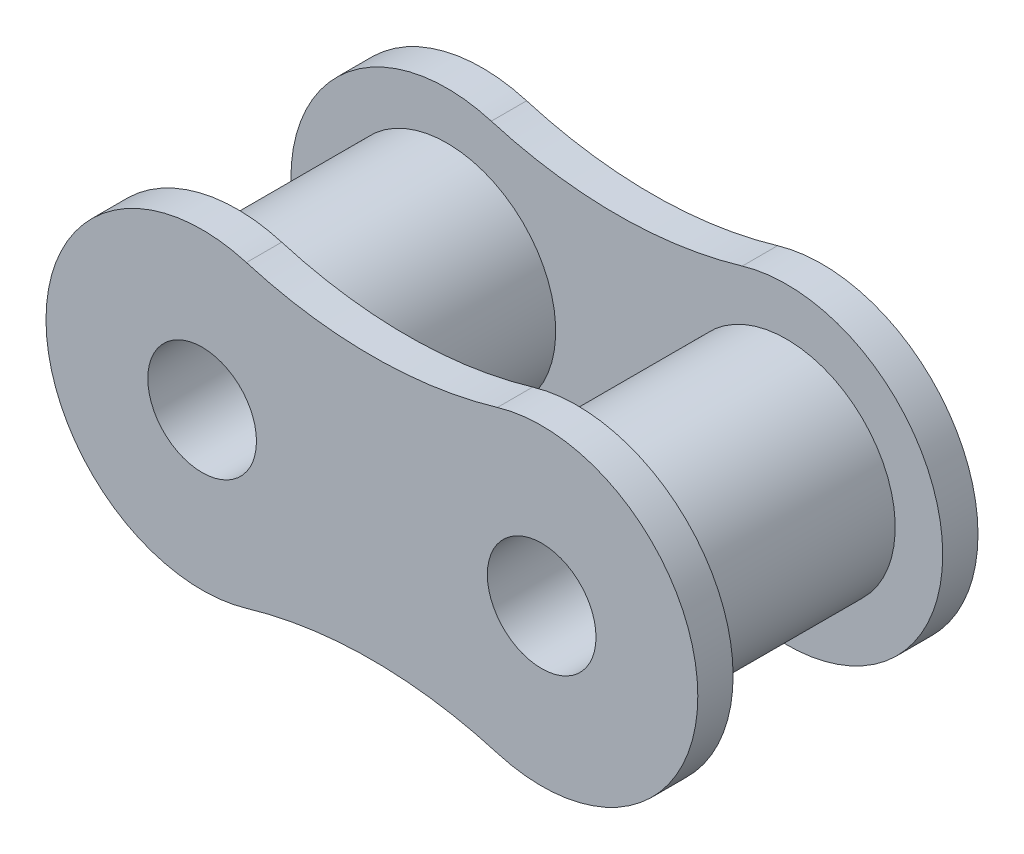
SolidWorks part; units mm, degrees
ref_plane "Front Plane" through (0, 0, 0) normal (0, 0, 1) x (1, 0, 0)
ref_plane "Top Plane" through (0, 0, 0) normal (0, 1, 0) x (1, 0, 0)
ref_plane "Right Plane" through (0, 0, 0) normal (1, 0, 0) x (0, 0, -1)
ref_axis "Axis_X" through (-24.6988, 0, 0) along (1, 0, 0)
ref_axis "Axis_Y" through (0, 8.03, 0) along (0, -1, 0)
ref_axis "Axis_Z" through (0, 0, -7.205) along (0, 0, 1)
sketch "Sketch1" plane through (0, 0, 0) normal (0, 0, 1) x (1, 0, 0)
  line L0 (0, 0) -> (-15.875, 0) construction
  line L1 (0, 5.08) -> (0, -5.08) construction
  circle A0 centre (0, 0) radius 2.54
  circle A1 centre (0, 0) radius 5.08
  circle A2 centre (-15.875, 0) radius 2.54
  circle A3 centre (-15.875, 0) radius 5.08
  dimension "FIX_41" = 5.08
  dimension "FIX_42" = 10.16
  dimension "FIX_43" = 15.875
extrude "Boss-Extrude1" add sketch "Sketch1" along normal mid plane 9.8
sketch "Sketch2" plane through (0, 0, 4.9) normal (0, 0, 1) x (1, 0, 0)
  line L0 (-15.875, 0) -> (0, 0) construction
  circle A0 centre (0, 0) radius 2.54
  circle A1 centre (-15.875, 0) radius 2.54
  arc A2 (-2.0702, -7.0003) -> (-2.0702, 7.0003) centre (0, 0) ccw
  arc A3 (-13.8048, 7.0003) -> (-13.8048, -7.0003) centre (-15.875, 0) ccw
  arc A4 (-13.8048, 7.0003) -> (-2.0702, 7.0003) centre (-7.9375, 26.8409) ccw
  arc A5 (-13.8048, -7.0003) -> (-2.0702, -7.0003) centre (-7.9375, -26.8409) cw
  dimension "FIX_45" = 5.08
  dimension "FIX_46" = 14.6
  dimension "FIX_47" = 20.69
extrude "Boss-Extrude2" add sketch "Sketch2" along normal blind 1.65
sketch "Sketch3" plane through (0, 0, -4.9) normal (0, 0, -1) x (-1, 0, 0)
  circle A0 centre (0, 0) radius 2.54
  circle A1 centre (15.875, 0) radius 2.54
  arc A2 (2.0702, 7.0003) -> (2.0702, -7.0003) centre (0, 0) ccw
  arc A3 (13.8048, -7.0003) -> (13.8048, 7.0003) centre (15.875, 0) ccw
  arc A4 (2.0702, 7.0003) -> (13.8048, 7.0003) centre (7.9375, 26.8409) ccw
  arc A5 (2.0702, -7.0003) -> (13.8048, -7.0003) centre (7.9375, -26.8409) cw
  dimension "FIX_49" = 5.08
extrude "Boss-Extrude3" add sketch "Sketch3" along normal blind 1.65
equation "\"Factor\"= 1.082532"
